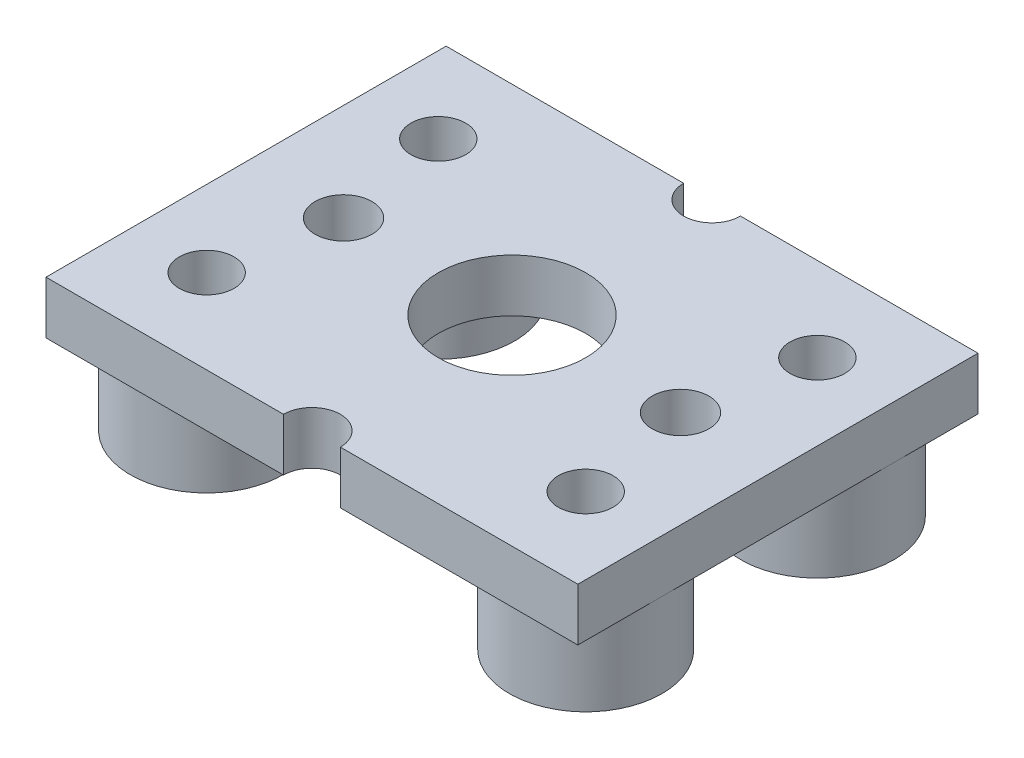
SolidWorks part; units mm, degrees
ref_plane "Front Plane" through (0, 0, 0) normal (0, 0, 1) x (1, 0, 0)
ref_plane "Top Plane" through (0, 0, 0) normal (0, 1, 0) x (1, 0, 0)
ref_plane "Right Plane" through (0, 0, 0) normal (1, 0, 0) x (0, 0, -1)
sketch "Sketch1" plane through (0, 0, 0) normal (0, 1, 0) x (1, 0, 0)
  line L1 (-14.5033, -14.9157) -> (14.5033, -14.9157)
  line L2 (-14.5033, -14.9157) -> (-14.5033, 14.9157)
  line L3 (-14.5033, 14.9157) -> (14.5033, 14.9157)
  line L4 (14.5033, -14.9157) -> (14.5033, 14.9157)
  line L5 (-14.5033, -14.9157) -> (14.5033, 14.9157) construction
  line L6 (-14.5033, 14.9157) -> (14.5033, -14.9157) construction
  line L7 (-9, -5.5) -> (9, -5.5) construction
  line L8 (-9, -5.5) -> (-9, 5.5) construction
  line L9 (-9, 5.5) -> (9, 5.5) construction
  line L10 (9, -5.5) -> (9, 5.5) construction
  line L11 (-9, -5.5) -> (9, 5.5) construction
  line L12 (-9, 5.5) -> (9, -5.5) construction
  circle A0 centre (9, 5.5) radius 1.3
  circle A1 centre (9, -5.5) radius 1.3
  circle A2 centre (-9, -5.5) radius 1.3
  circle A3 centre (-9, 5.5) radius 1.3
  circle A4 centre (0, 0) radius 3.5
  point P0 (0, 0)
  point P6 (0, 0)
  dimension "D4" = 2.6
  dimension "D1" = 7
  dimension "D3" = 11
  dimension "D5" = 18
extrude "BoardMountHoles" add sketch "Sketch1" along normal blind 2.5 contours L4 L3 L2 L1
extrude "BoardMounts" cut sketch "Sketch1<3>" along normal through all contours A0 | A1 | A2 | A3
sketch "Sketch1<3>" plane through (0, 0, 0) normal (0, 1, 0) x (1, 0, 0) same geometry as "Sketch1"
sketch "Sketch3" plane through (0, 0, 0) normal (0, -1, 0) x (1, 0, 0)
  circle A0 centre (9, 5.5) radius 3.6271
  circle A1 centre (9, -5.5) radius 3.6271
  circle A2 centre (-9, -5.5) radius 3.6271
  circle A3 centre (-9, 5.5) radius 3.6271
  circle A4 centre (-9, 5.5) radius 1.3 construction
  circle A5 centre (-9, -5.5) radius 1.3 construction
  circle A6 centre (9, -5.5) radius 1.3 construction
  circle A7 centre (9, 5.5) radius 1.3 construction
  circle A8 centre (-9, 5.5) radius 1.3
  circle A9 centre (-9, -5.5) radius 1.3
  circle A10 centre (9, -5.5) radius 1.3
  circle A11 centre (9, 5.5) radius 1.3
extrude "BoardStandoffs" add sketch "Sketch3" along normal blind 4
sketch "Sketch4" plane through (0, -4, 0) normal (0, -1, 0) x (1, 0, 0)
  line L1 (12.1754, -5.5) -> (10.5877, -2.75)
  line L2 (10.5877, -2.75) -> (7.4123, -2.75)
  line L3 (7.4123, -2.75) -> (5.8246, -5.5)
  line L4 (5.8246, -5.5) -> (7.4123, -8.25)
  line L5 (7.4123, -8.25) -> (10.5877, -8.25)
  line L6 (10.5877, -8.25) -> (12.1754, -5.5)
  line L7 (-5.8246, -5.5) -> (-7.4123, -2.75)
  line L8 (-7.4123, -2.75) -> (-10.5877, -2.75)
  line L9 (-10.5877, -2.75) -> (-12.1754, -5.5)
  line L10 (-12.1754, -5.5) -> (-10.5877, -8.25)
  line L11 (-10.5877, -8.25) -> (-7.4123, -8.25)
  line L12 (-7.4123, -8.25) -> (-5.8246, -5.5)
  line L13 (-5.8246, 5.5) -> (-7.4123, 8.25)
  line L14 (-7.4123, 8.25) -> (-10.5877, 8.25)
  line L15 (-10.5877, 8.25) -> (-12.1754, 5.5)
  line L16 (-12.1754, 5.5) -> (-10.5877, 2.75)
  line L17 (-10.5877, 2.75) -> (-7.4123, 2.75)
  line L18 (-7.4123, 2.75) -> (-5.8246, 5.5)
  line L19 (12.1754, 5.5) -> (10.5877, 8.25)
  line L20 (10.5877, 8.25) -> (7.4123, 8.25)
  line L21 (7.4123, 8.25) -> (5.8246, 5.5)
  line L22 (5.8246, 5.5) -> (7.4123, 2.75)
  line L23 (7.4123, 2.75) -> (10.5877, 2.75)
  line L24 (10.5877, 2.75) -> (12.1754, 5.5)
  circle A0 centre (9, -5.5) radius 2.75 construction
  circle A1 centre (-9, -5.5) radius 2.75 construction
  circle A2 centre (-9, 5.5) radius 2.75 construction
  circle A3 centre (9, 5.5) radius 2.75 construction
  dimension "D1" = 5.5
  dimension "D2" = 5.5
  dimension "D3" = 5.5
  dimension "D4" = 5.5
extrude "NutCutout" cut sketch "Sketch4" against normal blind 2
extrude "MagnetHole" cut sketch "Sketch1<4>" along normal through all contours A4
sketch "Sketch1<4>" plane through (0, 0, 0) normal (0, 1, 0) x (1, 0, 0) same geometry as "Sketch1"
sketch "Sketch2" plane through (0, 2.5, 0) normal (0, 1, 0) x (1, 0, 0)
  line L0 (0, 9.5) -> (0, -9.5) construction
  line L5 (8, 0) -> (-8, 0) construction
  circle A0 centre (8, 0) radius 1.35
  circle A2 centre (0, 9.5) radius 1.35
  circle A9 centre (-8, 0) radius 1.35
  circle A10 centre (0, -9.5) radius 1.35
  point P7 (0, 0)
  dimension "D3" = 2.7
  dimension "D1" = 19
  dimension "D2" = 16
extrude "MotorMountHoles" cut sketch "Sketch2" against normal through all
sketch "Sketch5" plane through (0, 0, 0) normal (0, -1, 0) x (1, 0, 0)
  line L1 (-12.6271, -9.5) -> (12.6271, -9.5)
  line L2 (-12.6271, -9.5) -> (-12.6271, 9.5)
  line L3 (-12.6271, 9.5) -> (12.6271, 9.5)
  line L4 (12.6271, -9.5) -> (12.6271, 9.5)
  circle A0 centre (9, -5.5) radius 3.6271 construction
  circle A1 centre (0, -9.5) radius 1.35
  circle A2 centre (0, -9.5) radius 1.35
  circle A3 centre (0, 9.5) radius 1.35
  circle A4 centre (0, 9.5) radius 1.35
  circle A5 centre (9, 5.5) radius 3.6271 construction
  circle A6 centre (-9, 5.5) radius 3.6271 construction
  circle A7 centre (-9, -5.5) radius 3.6271 construction
  circle A8 centre (9, -5.5) radius 3.6271
  circle A9 centre (9, 5.5) radius 3.6271
  circle A10 centre (-9, 5.5) radius 3.6271
  circle A11 centre (-9, -5.5) radius 3.6271
  dimension "D1" = 0
  dimension "D2" = 0
extrude "Cut-Extrude4" cut sketch "Sketch5" against normal through all flip side to cut contours L1 L4 L3 L2
equation "\"D2@Sketch4\"=\"D1@Sketch4\""
equation "\"D3@Sketch4\"=\"D1@Sketch4\""
equation "\"D4@Sketch4\"=\"D1@Sketch4\""
